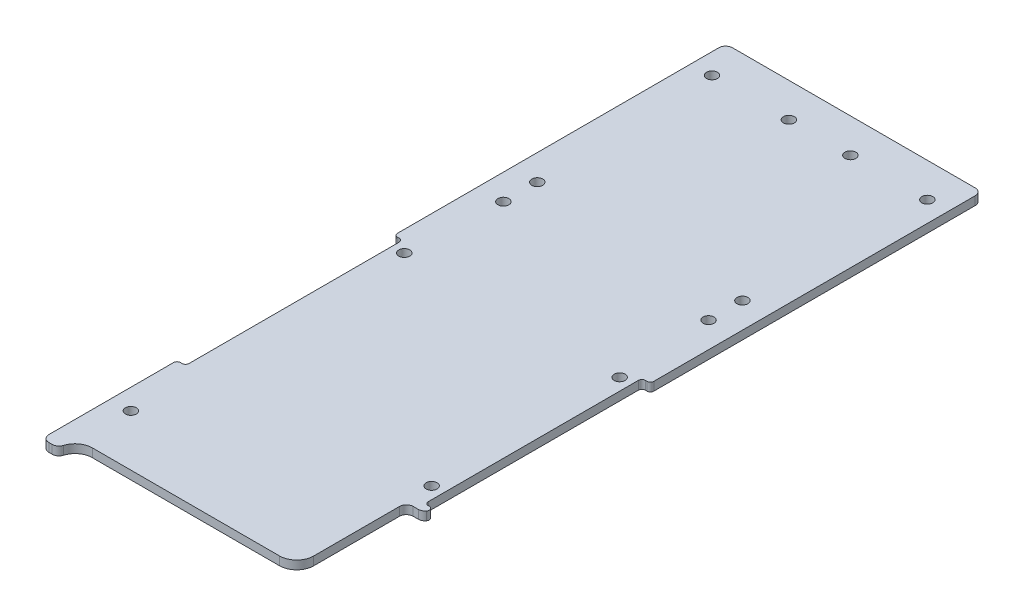
SolidWorks part; units mm, degrees
ref_plane "Front Plane" through (0, 0, 0) normal (0, 0, 1) x (1, 0, 0)
ref_plane "Top Plane" through (0, 0, 0) normal (0, 1, 0) x (1, 0, 0)
ref_plane "Right Plane" through (0, 0, 0) normal (1, 0, 0) x (0, 0, -1)
sketch "Sketch1" plane through (0, 0, 0) normal (0, 1, 0) x (1, 0, 0)
  line L0 (-39.9997, 0) -> (-39.9997, 114.3) construction
  line L1 (-47.625, 127) -> (47.625, 127)
  line L2 (-47.625, 127) -> (-47.625, -127)
  line L3 (-47.625, -127) -> (47.625, -127)
  line L4 (47.625, 127) -> (47.625, -127)
  line L5 (-47.625, 127) -> (47.625, -127) construction
  line L6 (-47.625, -127) -> (47.625, 127) construction
  line L7 (0, 0) -> (0, 127) construction
  line L8 (-39.9997, 0) -> (-39.9997, -101.6) construction
  line L9 (-39.9997, 0) -> (0, 0) construction
  line L10 (-41.275, -127) -> (-41.275, -120.65)
  line L11 (-41.275, -120.65) -> (41.275, -120.65)
  line L12 (41.275, -120.65) -> (41.275, -127)
  line L13 (-39.9997, 114.3) -> (-11.4247, 114.3) construction
  line L14 (39.9997, 114.3) -> (11.4247, 114.3) construction
  circle A0 centre (-39.9997, 114.3) radius 2.032
  circle A1 centre (-39.9997, 0) radius 2.032
  circle A2 centre (-39.9997, -101.6) radius 2.032
  circle A3 centre (39.9997, -101.6) radius 2.032
  circle A4 centre (39.9997, 0) radius 2.032
  circle A5 centre (39.9997, 114.3) radius 2.032
  circle A6 centre (-11.4247, 114.3) radius 2.032
  circle A7 centre (11.4247, 114.3) radius 2.032
  circle A8 centre (-39.9997, -69.85) radius 2.032
  circle A9 centre (39.9997, -69.85) radius 2.032
  point P0 (0, 0)
  dimension "D4" = 4.064
  dimension "D10" = 28.575
  dimension "D1" = 95.25
  dimension "D2" = 254
  dimension "D3" = 7.6253
  dimension "D5" = 12.7
  dimension "D6" = 25.4
  dimension "D7" = 6.35
  dimension "D8" = 6.35
  dimension "D9" = 6.35
  dimension "D11" = 69.85
extrude "Boss-Extrude1" add sketch "Sketch1" along normal blind 3.175 contours L4 L1 L2 L3 A4 A0 A1 A2 A3 A5 | A8 | A3 region at (0, 0, -2.6944) region at (39.9997, 0, 101.6) region at (-39.9997, 0, 69.85)
fillet "Fillet1" radius 2.54 4 edges at (-47.625, 1.5875, -127) (47.625, 1.5875, -127) (47.625, 1.5875, 127) (-47.625, 1.5875, 127)
fillet "Fillet2" radius 2.54 2 edges at (41.275, 1.5875, 127) (-41.275, 1.5875, 127)
fillet "Fillet3" radius 6.35 2 edges at (41.275, 1.5875, 120.65) (-41.275, 1.5875, 120.65)
sketch "Sketch2" plane through (0, 0, 0) normal (0, -1, 0) x (1, 0, 0)
  line L1 (43.815, 127) -> (45.085, 127) construction
  line L2 (40.6451, 123.5787) -> (40.6451, 79.8881)
  line L3 (40.6451, 79.8881) -> (47.625, 79.8881)
  line L11 (47.625, -124.46) -> (47.625, 124.46) construction
  line L12 (43.815, 127) -> (45.085, 127)
  line L13 (47.625, 79.8881) -> (47.625, 124.46)
  arc A0 (35.2956, 120.65) -> (41.3809, 125.1857) centre (35.2956, 127) ccw construction
  arc A1 (43.815, 127) -> (41.3809, 125.1857) centre (43.815, 124.46) ccw construction
  arc A2 (47.625, 124.46) -> (45.085, 127) centre (45.085, 124.46) ccw construction
  arc A3 (40.6451, 123.5787) -> (41.3809, 125.1857) centre (35.2956, 127) ccw
  arc A4 (43.815, 127) -> (41.3809, 125.1857) centre (43.815, 124.46) ccw
  arc A5 (47.625, 124.46) -> (45.085, 127) centre (45.085, 124.46) ccw
  dimension "D2" = 47.1119
  dimension "D1" = 6.9799
extrude "Cut-Extrude1" cut sketch "Sketch2" against normal through all
fillet "Fillet4" radius 6.35 1 edges at (40.6451, 1.5875, 123.5787)
fillet "Fillet5" radius 2.54 2 edges at (47.625, 1.5875, 79.8881) (40.6451, 1.5875, 79.8881)
sketch "Sketch3" plane through (0, 0, 0) normal (0, -1, 0) x (1, 0, 0)
  line L0 (-36.3021, -49.7791) -> (-39.9089, -49.7791) construction
  line L1 (-40.4169, -49.276) -> (-40.4169, -45.7043) construction
  line L2 (-35.7941, -45.7043) -> (-35.7941, -49.276) construction
  line L3 (-39.9089, -45.2013) -> (-36.3021, -45.2013) construction
  line L4 (-36.3021, -37.2027) -> (-39.9089, -37.2027) construction
  line L5 (-35.7941, -33.1279) -> (-35.7941, -36.6996) construction
  line L6 (-40.4169, -36.6996) -> (-40.4169, -33.1279) construction
  line L7 (-39.9089, -32.6249) -> (-36.3021, -32.6249) construction
  line L8 (36.2911, -32.6249) -> (39.8979, -32.6249) construction
  line L9 (40.4059, -33.1279) -> (40.4059, -36.6996) construction
  line L10 (39.8979, -37.2027) -> (36.2911, -37.2027) construction
  line L11 (35.7831, -36.6996) -> (35.7831, -33.1279) construction
  line L12 (36.2911, -45.2013) -> (39.8979, -45.2013) construction
  line L13 (35.7831, -49.276) -> (35.7831, -45.7043) construction
  line L14 (40.4059, -45.7043) -> (40.4059, -49.276) construction
  line L15 (39.8979, -49.7791) -> (36.2911, -49.7791) construction
  line L16 (-36.3021, -49.7791) -> (-39.9089, -49.7791)
  line L17 (-40.4169, -49.276) -> (-40.4169, -45.7043)
  line L18 (-35.7941, -45.7043) -> (-35.7941, -49.276)
  line L19 (-39.9089, -45.2013) -> (-36.3021, -45.2013)
  line L20 (-36.3021, -37.2027) -> (-39.9089, -37.2027)
  line L21 (-35.7941, -33.1279) -> (-35.7941, -36.6996)
  line L22 (-40.4169, -36.6996) -> (-40.4169, -33.1279)
  line L23 (-39.9089, -32.6249) -> (-36.3021, -32.6249)
  line L24 (36.2911, -32.6249) -> (39.8979, -32.6249)
  line L25 (40.4059, -33.1279) -> (40.4059, -36.6996)
  line L26 (39.8979, -37.2027) -> (36.2911, -37.2027)
  line L27 (35.7831, -36.6996) -> (35.7831, -33.1279)
  line L28 (36.2911, -45.2013) -> (39.8979, -45.2013)
  line L29 (35.7831, -49.276) -> (35.7831, -45.7043)
  line L30 (40.4059, -45.7043) -> (40.4059, -49.276)
  line L31 (39.8979, -49.7791) -> (36.2911, -49.7791)
  line L32 (-47.625, -25.836) -> (47.625, -25.836)
  line L33 (-47.625, -124.46) -> (-47.625, 124.46) construction
  line L34 (47.625, -124.46) -> (47.625, 77.3481) construction
  line L35 (0, -25.836) -> (0, -56.0686) construction
  line L1362 (-40.4169, -34.9138) -> (-35.7941, -34.9138)
  line L1857 (-38.1055, -32.6249) -> (-38.1055, -37.2027)
  line L1858 (-38.1055, -45.2013) -> (-38.1055, -49.7791)
  line L1859 (-40.4169, -47.4902) -> (-35.7941, -47.4902)
  circle A0 centre (-38.1055, -34.9138) radius 2.032
  circle A1 centre (-38.1055, -47.4902) radius 2.032
  circle A2 centre (38.1055, -47.4902) radius 2.032
  circle A3 centre (38.1055, -34.9138) radius 2.032
  ellipse E0 centre (-39.9089, -45.7043) end of major axis (-39.4009, -45.7043) minor radius 0.5031 (-39.9089, -45.2013) -> (-40.4169, -45.7043) ccw construction
  ellipse E1 centre (-39.9089, -49.276) end of major axis (-39.4009, -49.276) minor radius 0.5031 (-40.4169, -49.276) -> (-39.9089, -49.7791) ccw construction
  ellipse E6 centre (-36.3021, -49.276) end of major axis (-35.7941, -49.276) minor radius 0.5031 (-36.3021, -49.7791) -> (-35.7941, -49.276) ccw construction
  ellipse E7 centre (-36.3021, -45.7043) end of major axis (-35.7941, -45.7043) minor radius 0.5031 (-35.7941, -45.7043) -> (-36.3021, -45.2013) ccw construction
  ellipse E8 centre (-39.9089, -36.6996) end of major axis (-39.4009, -36.6996) minor radius 0.5031 (-40.4169, -36.6996) -> (-39.9089, -37.2027) ccw construction
  ellipse E9 centre (-36.3021, -36.6996) end of major axis (-35.7941, -36.6996) minor radius 0.5031 (-36.3021, -37.2027) -> (-35.7941, -36.6996) ccw construction
  ellipse E10 centre (-36.3021, -33.1279) end of major axis (-35.7941, -33.1279) minor radius 0.5031 (-35.7941, -33.1279) -> (-36.3021, -32.6249) ccw construction
  ellipse E11 centre (-39.9089, -33.1279) end of major axis (-39.4009, -33.1279) minor radius 0.5031 (-39.9089, -32.6249) -> (-40.4169, -33.1279) ccw construction
  ellipse E12 centre (39.8979, -33.1279) end of major axis (40.4059, -33.1279) minor radius 0.5031 (40.4059, -33.1279) -> (39.8979, -32.6249) ccw construction
  ellipse E13 centre (36.2911, -33.1279) end of major axis (36.7991, -33.1279) minor radius 0.5031 (36.2911, -32.6249) -> (35.7831, -33.1279) ccw construction
  ellipse E14 centre (39.8979, -36.6996) end of major axis (40.4059, -36.6996) minor radius 0.5031 (39.8979, -37.2027) -> (40.4059, -36.6996) ccw construction
  ellipse E15 centre (36.2911, -36.6996) end of major axis (36.7991, -36.6996) minor radius 0.5031 (35.7831, -36.6996) -> (36.2911, -37.2027) ccw construction
  ellipse E16 centre (36.2911, -45.7043) end of major axis (36.7991, -45.7043) minor radius 0.5031 (36.2911, -45.2013) -> (35.7831, -45.7043) ccw construction
  ellipse E17 centre (36.2911, -49.276) end of major axis (36.7991, -49.276) minor radius 0.5031 (35.7831, -49.276) -> (36.2911, -49.7791) ccw construction
  ellipse E18 centre (39.8979, -45.7043) end of major axis (40.4059, -45.7043) minor radius 0.5031 (40.4059, -45.7043) -> (39.8979, -45.2013) ccw construction
  ellipse E19 centre (39.8979, -49.276) end of major axis (40.4059, -49.276) minor radius 0.5031 (39.8979, -49.7791) -> (40.4059, -49.276) ccw construction
  ellipse E20 centre (-39.9089, -45.7043) end of major axis (-39.4009, -45.7043) minor radius 0.5031 (-39.9089, -45.2013) -> (-40.4169, -45.7043) ccw
  ellipse E21 centre (-39.9089, -49.276) end of major axis (-39.4009, -49.276) minor radius 0.5031 (-40.4169, -49.276) -> (-39.9089, -49.7791) ccw
  ellipse E22 centre (-36.3021, -49.276) end of major axis (-35.7941, -49.276) minor radius 0.5031 (-36.3021, -49.7791) -> (-35.7941, -49.276) ccw
  ellipse E23 centre (-36.3021, -45.7043) end of major axis (-35.7941, -45.7043) minor radius 0.5031 (-35.7941, -45.7043) -> (-36.3021, -45.2013) ccw
  ellipse E24 centre (-39.9089, -36.6996) end of major axis (-39.4009, -36.6996) minor radius 0.5031 (-40.4169, -36.6996) -> (-39.9089, -37.2027) ccw
  ellipse E25 centre (-36.3021, -36.6996) end of major axis (-35.7941, -36.6996) minor radius 0.5031 (-36.3021, -37.2027) -> (-35.7941, -36.6996) ccw
  ellipse E26 centre (-36.3021, -33.1279) end of major axis (-35.7941, -33.1279) minor radius 0.5031 (-35.7941, -33.1279) -> (-36.3021, -32.6249) ccw
  ellipse E27 centre (-39.9089, -33.1279) end of major axis (-39.4009, -33.1279) minor radius 0.5031 (-39.9089, -32.6249) -> (-40.4169, -33.1279) ccw
  ellipse E28 centre (39.8979, -33.1279) end of major axis (40.4059, -33.1279) minor radius 0.5031 (40.4059, -33.1279) -> (39.8979, -32.6249) ccw
  ellipse E29 centre (36.2911, -33.1279) end of major axis (36.7991, -33.1279) minor radius 0.5031 (36.2911, -32.6249) -> (35.7831, -33.1279) ccw
  ellipse E30 centre (39.8979, -36.6996) end of major axis (40.4059, -36.6996) minor radius 0.5031 (39.8979, -37.2027) -> (40.4059, -36.6996) ccw
  ellipse E31 centre (36.2911, -36.6996) end of major axis (36.7991, -36.6996) minor radius 0.5031 (35.7831, -36.6996) -> (36.2911, -37.2027) ccw
  ellipse E32 centre (36.2911, -45.7043) end of major axis (36.7991, -45.7043) minor radius 0.5031 (36.2911, -45.2013) -> (35.7831, -45.7043) ccw
  ellipse E33 centre (36.2911, -49.276) end of major axis (36.7991, -49.276) minor radius 0.5031 (35.7831, -49.276) -> (36.2911, -49.7791) ccw
  ellipse E34 centre (39.8979, -45.7043) end of major axis (40.4059, -45.7043) minor radius 0.5031 (40.4059, -45.7043) -> (39.8979, -45.2013) ccw
  ellipse E35 centre (39.8979, -49.276) end of major axis (40.4059, -49.276) minor radius 0.5031 (39.8979, -49.7791) -> (40.4059, -49.276) ccw
  dimension "D2" = 4.064
extrude "Cut-Extrude2" cut sketch "Sketch3" against normal through all contours A0 | A1 | A2 | A3
sketch "Sketch4" plane through (0, 3.175, 0) normal (0, 1, 0) x (1, 0, 0)
  line L11 (-47.625, 124.46) -> (-47.625, -124.46) construction
  line L12 (-47.625, -76.835) -> (-44.45, -76.835)
  line L13 (-47.625, -76.835) -> (-47.625, 3.81)
  line L15 (-47.625, 3.81) -> (-44.45, 3.81)
  line L16 (-44.45, -76.835) -> (-44.45, 3.81)
  line L17 (47.625, 124.46) -> (47.625, -77.3481) construction
  line L18 (47.625, -76.835) -> (44.45, -76.835)
  line L19 (47.625, -76.835) -> (47.625, 3.81)
  line L20 (47.625, 3.81) -> (44.45, 3.81)
  line L45 (44.45, -76.835) -> (44.45, 3.81)
  line L47 (43.1851, -79.8881) -> (45.085, -79.8881) construction
  dimension "D1" = 3.175
  dimension "D2" = 80.645
  dimension "D3" = 3.0531
extrude "Cut-Extrude3" cut sketch "Sketch4" against normal through all and the other way through all
fillet "Fillet6" radius 1.27 8 edges at (-44.45, 1.5875, -3.81) (-47.625, 1.5875, -3.81) (-47.625, 1.5875, 76.835) (-44.45, 1.5875, 76.835) (44.45, 1.5875, 76.835) (47.625, 1.5875, 76.835) (44.45, 1.5875, -3.81) (47.625, 1.5875, -3.81)
